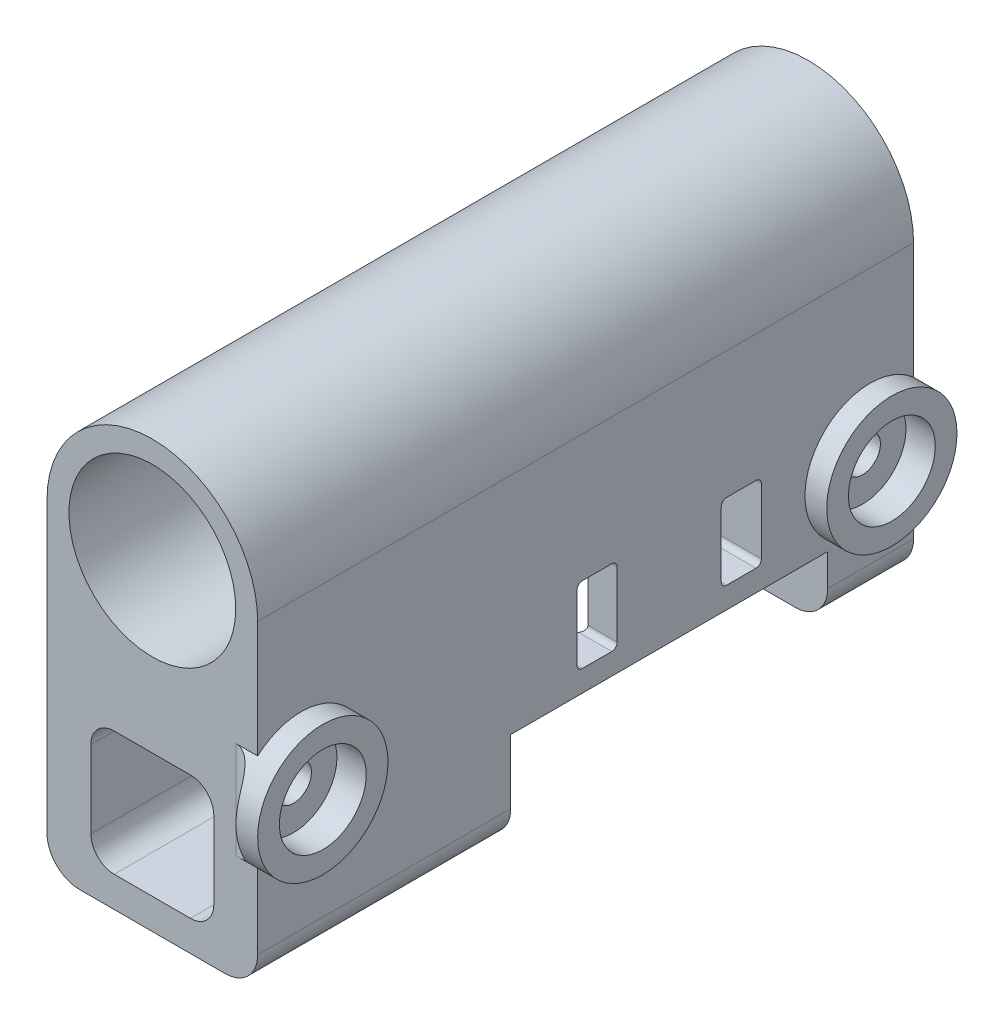
SolidWorks part; units mm, degrees
ref_plane "Front Plane" through (0, 0, 0) normal (0, 0, 1) x (1, 0, 0)
ref_plane "Top Plane" through (0, 0, 0) normal (0, 1, 0) x (1, 0, 0)
ref_plane "Right Plane" through (0, 0, 0) normal (1, 0, 0) x (0, 0, -1)
sketch "Sketch1" plane through (0, 0, 0) normal (0, 0, 1) x (1, 0, 0)
  line L24 (9.7, 0) -> (9.7, -26.58)
  line L54 (-9.7, 0) -> (-9.7, -26.58)
  line L55 (6.7, -29.58) -> (-6.7, -29.58)
  circle A1 centre (0, 0) radius 7.68
  arc A17 (9.7, 0) -> (-9.7, 0) centre (0, 0) ccw
  arc A51 (9.7, -26.58) -> (6.7, -29.58) centre (6.7, -26.58) cw
  arc A52 (-9.7, -26.58) -> (-6.7, -29.58) centre (-6.7, -26.58) ccw
extrude "Boss-Extrude1" add sketch "Sketch1" along normal blind 60.4
sketch "Sketch16" plane through (0, 0, 0) normal (0, 0, -1) x (-1, 0, 0)
  line L0 (-6.7, -29.58) -> (6.7, -29.58)
  line L1 (-9.7, -23.62) -> (-9.7, -26.58)
  line L3 (9.7, -23.62) -> (9.7, -26.58)
  line L5 (-6.7, -26.62) -> (6.7, -26.62)
  arc A0 (-9.7, -26.58) -> (-6.7, -29.58) centre (-6.7, -26.58) ccw
  arc A1 (6.7, -29.58) -> (9.7, -26.58) centre (6.7, -26.58) ccw
  arc A2 (-9.7, -23.62) -> (-6.7, -26.62) centre (-6.7, -23.62) ccw
  arc A3 (6.7, -26.62) -> (9.7, -23.62) centre (6.7, -23.62) ccw
extrude "Cut-Extrude10" cut sketch "Sketch16" against normal offset from surface (30.4 mm away) 30 up to face at (0, -17.3104, 60.4)
sketch "Sketch4" plane through (0, -26.62, 0) normal (0, -1, 0) x (1, 0, 0)
  circle A0 centre (0, 22.5) radius 8.49
extrude "Cut-Extrude2" cut sketch "Sketch4" against normal blind 11 from offset 5.95 offset against normal yes
sketch "Sketch5" plane through (0, -29.58, 0) normal (0, -1, 0) x (1, 0, 0)
  circle A0 centre (0, 22.5) radius 2.5
  circle A1 centre (5.56, 33.0942) radius 1.65
  circle A2 centre (5.56, 11.9058) radius 1.65
  circle A3 centre (-5.56, 11.9058) radius 1.65
  circle A4 centre (-5.56, 33.0942) radius 1.65
extrude "Cut-Extrude3" cut sketch "Sketch5" against normal up to surface (21.9 mm away) up to face at (7.68, 0, 60.4)
sketch "Sketch3" plane through (9.7, 0, 0) normal (1, 0, 0) x (0, 0, -1)
  line L26 (-30.49, -11.7) -> (-27.79, -11.7)
  line L27 (-30.99, -12.2) -> (-30.99, -18.2)
  line L28 (-30.49, -18.7) -> (-27.79, -18.7)
  line L29 (-27.29, -12.2) -> (-27.29, -18.2)
  line L36 (-17.21, -11.7) -> (-14.51, -11.7)
  line L37 (-17.71, -12.2) -> (-17.71, -18.2)
  line L38 (-17.21, -18.7) -> (-14.51, -18.7)
  line L39 (-14.01, -12.2) -> (-14.01, -18.2)
  arc A24 (-14.51, -11.7) -> (-14.01, -12.2) centre (-14.51, -12.2) cw
  arc A25 (-14.51, -18.7) -> (-14.01, -18.2) centre (-14.51, -18.2) ccw
  arc A26 (-17.71, -18.2) -> (-17.21, -18.7) centre (-17.21, -18.2) ccw
  arc A27 (-17.21, -11.7) -> (-17.71, -12.2) centre (-17.21, -12.2) ccw
  arc A28 (-27.79, -11.7) -> (-27.29, -12.2) centre (-27.79, -12.2) cw
  arc A29 (-27.79, -18.7) -> (-27.29, -18.2) centre (-27.79, -18.2) ccw
  arc A30 (-30.99, -18.2) -> (-30.49, -18.7) centre (-30.49, -18.2) ccw
  arc A31 (-30.49, -11.7) -> (-30.99, -12.2) centre (-30.49, -12.2) ccw
  circle A32 centre (-4, -15.2) radius 1.65
  circle A33 centre (-56.4, -15.2) radius 1.65
extrude "Cut-Extrude1" cut sketch "Sketch3" against normal up to next
sketch "Sketch6" plane through (0, -29.58, 0) normal (0, -1, 0) x (1, 0, 0)
  line L42 (-9.7, 37.0942) -> (9.7, 37.0942)
  line L43 (-9.7, 37.0942) -> (-9.7, 7.9058)
  line L44 (-9.7, 7.9058) -> (9.7, 7.9058)
  line L45 (9.7, 37.0942) -> (9.7, 7.9058)
extrude "Cut-Extrude4" cut sketch "Sketch6" against normal up to surface (8.91 mm away) up to face at (0, -20.67, 20)
sketch "Sketch7" plane through (0, -9.67, 0) normal (0, -1, 0) x (1, 0, 0)
  circle A0 centre (0, 22.5) radius 2.5
  circle A1 centre (0, 22.5) radius 3.5
extrude "Boss-Extrude2" add sketch "Sketch7" along normal blind 0.4
sketch "Sketch8" plane through (0, 0, 0) normal (0, 0, -1) x (-1, 0, 0)
  line L0 (3.5, -18) -> (3.5, -18.7)
  line L1 (3, -17.5) -> (-3, -17.5)
  line L2 (-3.5, -18) -> (-3.5, -18.7)
  line L3 (3, -19.2) -> (-3, -19.2)
  arc A0 (-3, -19.2) -> (-3.5, -18.7) centre (-3, -18.7) cw
  arc A1 (-3, -17.5) -> (-3.5, -18) centre (-3, -18) ccw
  arc A2 (3.5, -18.7) -> (3, -19.2) centre (3, -18.7) cw
  arc A3 (3, -17.5) -> (3.5, -18) centre (3, -18) cw
extrude "Cut-Extrude5" cut sketch "Sketch8" against normal up to next
sketch "Sketch25" plane through (0, 0, 0) normal (0, 0, -1) x (-1, 0, 0)
  line L5 (-3, -16.7) -> (3, -16.7)
  line L6 (-3.5, -17.2) -> (-3.5, -18.7)
  line L7 (-3, -19.2) -> (3, -19.2)
  line L8 (3.5, -17.2) -> (3.5, -18.7)
  arc A4 (3, -19.2) -> (3.5, -18.7) centre (3, -18.7) ccw
  arc A5 (3.5, -17.2) -> (3, -16.7) centre (3, -17.2) ccw
  arc A6 (-3, -16.7) -> (-3.5, -17.2) centre (-3, -17.2) ccw
  arc A7 (-3, -19.2) -> (-3.5, -18.7) centre (-3, -18.7) cw
extrude "Cut-Extrude14" cut sketch "Sketch25" against normal up to next from offset 7 offset against normal yes
sketch "Sketch9" plane through (0, 0, 60.4) normal (0, 0, 1) x (1, 0, 0)
  line L12 (3.51, -26.77) -> (-3.51, -26.77)
  line L17 (5.66, -24.62) -> (5.66, -17.49)
  line L18 (3.51, -15.34) -> (-3.51, -15.34)
  line L19 (-5.66, -24.62) -> (-5.66, -17.49)
  arc A13 (-3.51, -15.34) -> (-5.66, -17.49) centre (-3.51, -17.49) ccw
  arc A14 (5.66, -17.49) -> (3.51, -15.34) centre (3.51, -17.49) ccw
  arc A15 (-3.51, -26.77) -> (-5.66, -24.62) centre (-3.51, -24.62) cw
  arc A16 (3.51, -26.77) -> (5.66, -24.62) centre (3.51, -24.62) ccw
sketch "Sketch11" plane through (0, 0, 60.4) normal (0, 0, 1) x (1, 0, 0)
  circle A1 centre (0, -22.91) radius 1.7
extrude "Cut-Extrude8" cut sketch "Sketch9" against normal up to surface (23.3058 mm away) up to face at (0, -25.8171, 37.0942)
sketch "Sketch14" plane through (-9.7, 0, 0) normal (-1, 0, 0) x (0, 0, 1)
  circle A0 centre (4, -15.2) radius 3.3
  circle A1 centre (56.4, -15.2) radius 3.3
extrude "Cut-Extrude9" cut sketch "Sketch14" against normal blind 2
extrude "Cut-Extrude11" cut sketch "Sketch11" against normal up to surface (60.4 mm away) up to face at (0, -18.35, 0)
sketch "Sketch17" plane through (9.7, 0, 0) normal (1, 0, 0) x (0, 0, -1)
  circle A0 centre (-56.4, -15.2) radius 1.65
  circle A1 centre (-4, -15.2) radius 1.65
  circle A2 centre (-4, -15.2) radius 6
  circle A3 centre (-56.4, -15.2) radius 6
extrude "Boss-Extrude3" add sketch "Sketch17" along normal blind 2
fillet "Fillet1" radius 2 2 edges at (9.7, -15.2, 60.4) (9.7, -15.2, 0)
sketch "Sketch18" plane through (11.7, 0, 0) normal (1, 0, 0) x (0, 0, -1)
  circle A0 centre (-56.4, -15.2) radius 4
  circle A1 centre (-4, -15.2) radius 4
extrude "Cut-Extrude12" cut sketch "Sketch18" against normal blind 2.7
sketch "Sketch24" plane through (0, -20.67, 0) normal (0, -1, 0) x (1, 0, 0)
  line L1 (5.56, 29.7456) -> (8.46, 31.4199)
  line L2 (8.46, 31.4199) -> (8.46, 34.7685)
  line L3 (8.46, 34.7685) -> (5.56, 36.4429)
  line L4 (5.56, 36.4429) -> (2.66, 34.7685)
  line L5 (2.66, 34.7685) -> (2.66, 31.4199)
  line L6 (2.66, 31.4199) -> (5.56, 29.7456)
  line L7 (-5.56, 29.7456) -> (-2.66, 31.4199)
  line L8 (-2.66, 31.4199) -> (-2.66, 34.7685)
  line L9 (-2.66, 34.7685) -> (-5.56, 36.4429)
  line L10 (-5.56, 36.4429) -> (-8.46, 34.7685)
  line L11 (-8.46, 34.7685) -> (-8.46, 31.4199)
  line L12 (-8.46, 31.4199) -> (-5.56, 29.7456)
  line L13 (-5.56, 8.5571) -> (-2.66, 10.2315)
  line L14 (-2.66, 10.2315) -> (-2.66, 13.5801)
  line L15 (-2.66, 13.5801) -> (-5.56, 15.2544)
  line L16 (-5.56, 15.2544) -> (-8.46, 13.5801)
  line L17 (-8.46, 13.5801) -> (-8.46, 10.2315)
  line L18 (-8.46, 10.2315) -> (-5.56, 8.5571)
  line L19 (5.56, 8.5571) -> (8.46, 10.2315)
  line L20 (8.46, 10.2315) -> (8.46, 13.5801)
  line L21 (8.46, 13.5801) -> (5.56, 15.2544)
  line L22 (5.56, 15.2544) -> (2.66, 13.5801)
  line L23 (2.66, 13.5801) -> (2.66, 10.2315)
  line L24 (2.66, 10.2315) -> (5.56, 8.5571)
  circle A0 centre (5.56, 33.0942) radius 2.9 construction
  circle A1 centre (-5.56, 33.0942) radius 2.9 construction
  circle A2 centre (-5.56, 11.9058) radius 2.9 construction
  circle A3 centre (5.56, 11.9058) radius 2.9 construction
extrude "Cut-Extrude13" cut sketch "Sketch24" against normal blind 7 from offset 11 offset against normal yes
